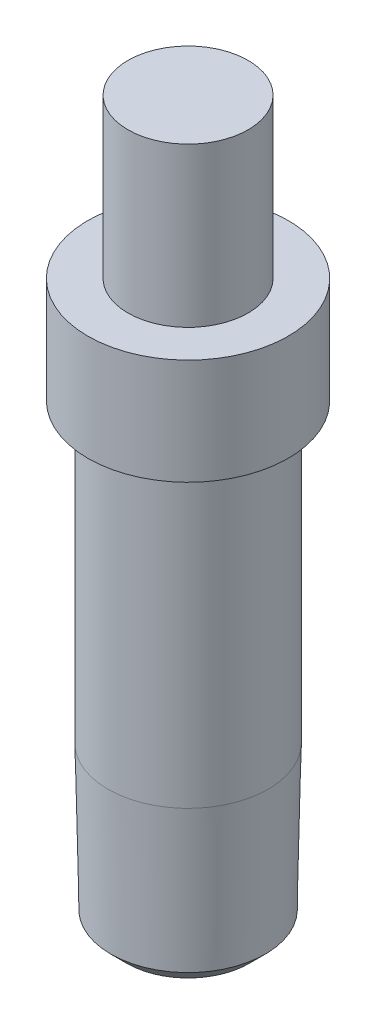
SolidWorks part; units mm, degrees
ref_plane "Front Plane" through (0, 0, 0) normal (0, 0, 1) x (1, 0, 0)
ref_plane "Top Plane" through (0, 0, 0) normal (0, 1, 0) x (1, 0, 0)
ref_plane "Right Plane" through (0, 0, 0) normal (1, 0, 0) x (0, 0, -1)
sketch "Sketch2" plane through (0, 0, 0) normal (0, 1, 0) x (1, 0, 0)
  circle A0 centre (0, 0) radius 1.25
  dimension "D1" = 2.5
extrude "Boss-Extrude1" add sketch "Sketch2" along normal blind 9
sketch "Sketch4" plane through (0, 0, 0) normal (0, 0, 1) x (1, 0, 0)
  line L0 (0, 9) -> (0, 0.1536) construction
  line L1 (1.25, 9) -> (-1.25, 9) construction
  line L2 (0.75, 9) -> (0.75, 7.02)
  line L3 (0.75, 7.02) -> (1.25, 7.02)
  line L4 (1.25, 0) -> (1.25, 9) construction
  line L5 (1.25, 7.02) -> (1.25, 5.7)
  line L6 (1.25, 5.7) -> (1, 5.7)
  line L7 (1, 5.7) -> (1, 2)
  line L8 (1, 2) -> (0.9639, 0.2)
  line L9 (0.75, 9) -> (1.75, 9)
  line L11 (0.9639, 0.2) -> (0.7639, 0)
  line L12 (-1.25, 0) -> (1.25, 0) construction
  line L13 (0.7639, 0) -> (1.75, 0)
  line L15 (1.75, 0) -> (1.75, 9)
  line L16 (1.75, 0) -> (1.75, 9)
  dimension "D1" = 3.3
  dimension "D2" = 1.32
  dimension "D3" = 1.5
  dimension "D4" = 2
  dimension "D5" = 2
  dimension "D6" = 0.2
  dimension "D7" = 45
  dimension "D8" = 1.15
  dimension "D9" = 0.5
revolve "Cut-Revolve1" cut sketch "Sketch4" angle 360 about L0
